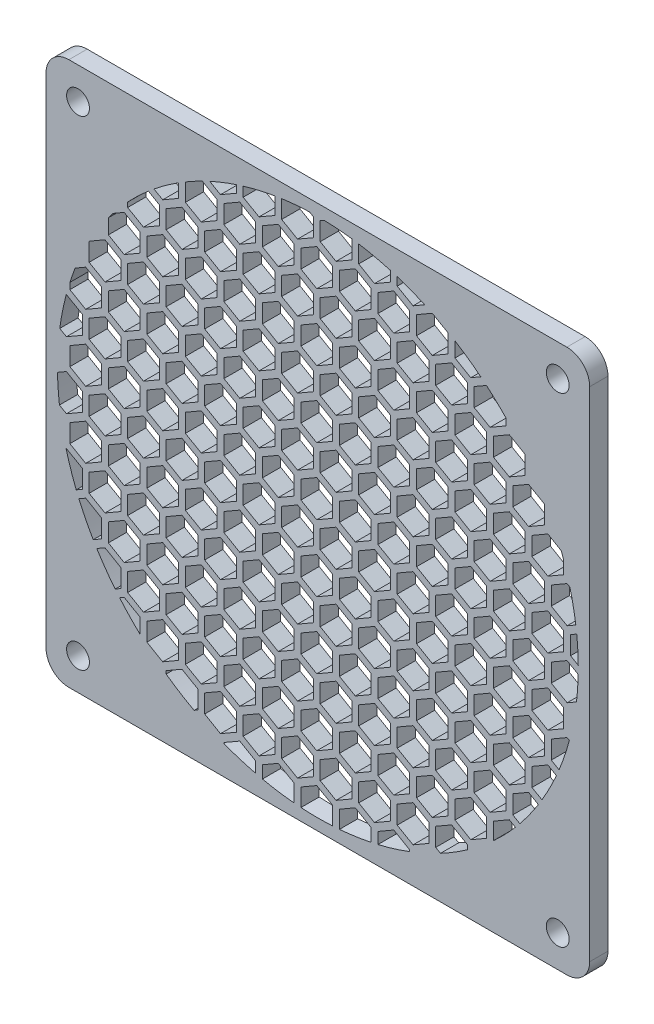
SolidWorks part; units mm, degrees
ref_plane "Plan de face" through (0, 0, 0) normal (0, 0, 1) x (1, 0, 0)
ref_plane "Plan de dessus" through (0, 0, 0) normal (0, 1, 0) x (1, 0, 0)
ref_plane "Plan de droite" through (0, 0, 0) normal (1, 0, 0) x (0, 0, -1)
sketch "Esquisse1" plane through (0, 0, 0) normal (0, 0, 1) x (1, 0, 0)
  line L1 (-59.5, 59.5) -> (59.5, 59.5)
  line L2 (-59.5, 59.5) -> (-59.5, -59.5)
  line L3 (-59.5, -59.5) -> (59.5, -59.5)
  line L4 (59.5, 59.5) -> (59.5, -59.5)
  line L5 (-59.5, 59.5) -> (59.5, -59.5) construction
  line L6 (-59.5, -59.5) -> (59.5, 59.5) construction
  line L47 (-30.4977, 48.1549) -> (-30.4977, 45.201)
  line L48 (-30.4977, 45.201) -> (-33.9618, 43.201)
  line L49 (-33.9618, 43.201) -> (-35.8669, 44.3009)
  line L58 (-25.3097, 51.0727) -> (-22.0677, 49.201)
  line L59 (-22.0677, 49.201) -> (-22.0677, 45.201)
  line L60 (-22.0677, 45.201) -> (-25.5318, 43.201)
  line L61 (-25.5318, 43.201) -> (-28.9959, 45.201)
  line L62 (-28.9959, 45.201) -> (-28.9959, 49.0738)
  line L66 (-17.8518, 54.1324) -> (-17.8518, 52.5)
  line L67 (-17.8518, 52.5) -> (-21.3159, 50.5)
  line L68 (-21.3159, 50.5) -> (-23.664, 51.8557)
  line L70 (-17.1018, 51.201) -> (-13.6377, 49.201)
  line L71 (-13.6377, 49.201) -> (-13.6377, 45.201)
  line L72 (-13.6377, 45.201) -> (-17.1018, 43.201)
  line L73 (-17.1018, 43.201) -> (-20.5659, 45.201)
  line L74 (-20.5659, 45.201) -> (-20.5659, 49.201)
  line L75 (-20.5659, 49.201) -> (-17.1018, 51.201)
  line L78 (-9.4218, 56.2159) -> (-9.4218, 52.5)
  line L79 (-9.4218, 52.5) -> (-12.8859, 50.5)
  line L80 (-12.8859, 50.5) -> (-16.35, 52.5)
  line L81 (-16.35, 52.5) -> (-16.35, 54.6047)
  line L82 (-8.6718, 51.201) -> (-5.2077, 49.201)
  line L83 (-5.2077, 49.201) -> (-5.2077, 45.201)
  line L84 (-5.2077, 45.201) -> (-8.6718, 43.201)
  line L85 (-8.6718, 43.201) -> (-12.1359, 45.201)
  line L86 (-12.1359, 45.201) -> (-12.1359, 49.201)
  line L87 (-12.1359, 49.201) -> (-8.6718, 51.201)
  line L89 (-1.8081, 56.9713) -> (-0.9918, 56.5)
  line L90 (-0.9918, 56.5) -> (-0.9918, 52.5)
  line L91 (-0.9918, 52.5) -> (-4.4559, 50.5)
  line L92 (-4.4559, 50.5) -> (-7.92, 52.5)
  line L93 (-7.92, 52.5) -> (-7.92, 56.4471)
  line L94 (-0.2418, 51.201) -> (3.2223, 49.201)
  line L95 (3.2223, 49.201) -> (3.2223, 45.201)
  line L96 (3.2223, 45.201) -> (-0.2418, 43.201)
  line L97 (-0.2418, 43.201) -> (-3.7059, 45.201)
  line L98 (-3.7059, 45.201) -> (-3.7059, 49.201)
  line L99 (-3.7059, 49.201) -> (-0.2418, 51.201)
  line L100 (0.51, 56.5) -> (1.3484, 56.984)
  line L101 (7.41, 56.5163) -> (7.4382, 56.5)
  line L102 (7.4382, 56.5) -> (7.4382, 52.5)
  line L103 (7.4382, 52.5) -> (3.9741, 50.5)
  line L104 (3.9741, 50.5) -> (0.51, 52.5)
  line L105 (0.51, 52.5) -> (0.51, 56.5)
  line L106 (8.1882, 51.201) -> (11.6523, 49.201)
  line L107 (11.6523, 49.201) -> (11.6523, 45.201)
  line L108 (11.6523, 45.201) -> (8.1882, 43.201)
  line L109 (8.1882, 43.201) -> (4.7241, 45.201)
  line L110 (4.7241, 45.201) -> (4.7241, 49.201)
  line L111 (4.7241, 49.201) -> (8.1882, 51.201)
  line L114 (15.8682, 54.7467) -> (15.8682, 52.5)
  line L115 (15.8682, 52.5) -> (12.4041, 50.5)
  line L116 (12.4041, 50.5) -> (8.94, 52.5)
  line L117 (8.94, 52.5) -> (8.94, 56.2946)
  line L118 (16.6182, 51.201) -> (20.0823, 49.201)
  line L119 (20.0823, 49.201) -> (20.0823, 45.201)
  line L120 (20.0823, 45.201) -> (16.6182, 43.201)
  line L121 (16.6182, 43.201) -> (13.1541, 45.201)
  line L122 (13.1541, 45.201) -> (13.1541, 49.201)
  line L123 (13.1541, 49.201) -> (16.6182, 51.201)
  line L127 (23.3941, 51.978) -> (20.8341, 50.5)
  line L128 (20.8341, 50.5) -> (17.37, 52.5)
  line L129 (17.37, 52.5) -> (17.37, 54.2889)
  line L130 (25.0482, 51.201) -> (28.5123, 49.201)
  line L131 (28.5123, 49.201) -> (28.5123, 45.201)
  line L132 (28.5123, 45.201) -> (25.0482, 43.201)
  line L133 (25.0482, 43.201) -> (21.5841, 45.201)
  line L134 (21.5841, 45.201) -> (21.5841, 49.201)
  line L135 (21.5841, 49.201) -> (25.0482, 51.201)
  line L144 (35.665, 44.4635) -> (33.4782, 43.201)
  line L145 (33.4782, 43.201) -> (30.0141, 45.201)
  line L146 (30.0141, 45.201) -> (30.0141, 48.4578)
  line L202 (-42.3918, 36.604) -> (-38.9277, 34.604)
  line L203 (-38.9277, 34.604) -> (-38.9277, 30.604)
  line L204 (-38.9277, 30.604) -> (-42.3918, 28.604)
  line L205 (-42.3918, 28.604) -> (-45.8559, 30.604)
  line L206 (-45.8559, 30.604) -> (-45.8559, 33.8561)
  line L207 (-44.8401, 35.1904) -> (-42.3918, 36.604)
  line L209 (-37.0941, 43.2785) -> (-34.7118, 41.903)
  line L210 (-34.7118, 41.903) -> (-34.7118, 37.903)
  line L211 (-34.7118, 37.903) -> (-38.1759, 35.903)
  line L212 (-38.1759, 35.903) -> (-41.64, 37.903)
  line L213 (-41.64, 37.903) -> (-41.64, 38.9244)
  line L214 (-33.9618, 36.604) -> (-30.4977, 34.604)
  line L215 (-30.4977, 34.604) -> (-30.4977, 30.604)
  line L216 (-30.4977, 30.604) -> (-33.9618, 28.604)
  line L217 (-33.9618, 28.604) -> (-37.4259, 30.604)
  line L218 (-37.4259, 30.604) -> (-37.4259, 34.604)
  line L219 (-37.4259, 34.604) -> (-33.9618, 36.604)
  line L220 (-33.21, 41.903) -> (-29.7459, 43.903)
  line L221 (-29.7459, 43.903) -> (-26.2818, 41.903)
  line L222 (-26.2818, 41.903) -> (-26.2818, 37.903)
  line L223 (-26.2818, 37.903) -> (-29.7459, 35.903)
  line L224 (-29.7459, 35.903) -> (-33.21, 37.903)
  line L225 (-33.21, 37.903) -> (-33.21, 41.903)
  line L226 (-25.5318, 36.604) -> (-22.0677, 34.604)
  line L227 (-22.0677, 34.604) -> (-22.0677, 30.604)
  line L228 (-22.0677, 30.604) -> (-25.5318, 28.604)
  line L229 (-25.5318, 28.604) -> (-28.9959, 30.604)
  line L230 (-28.9959, 30.604) -> (-28.9959, 34.604)
  line L231 (-28.9959, 34.604) -> (-25.5318, 36.604)
  line L232 (-24.78, 41.903) -> (-21.3159, 43.903)
  line L233 (-21.3159, 43.903) -> (-17.8518, 41.903)
  line L234 (-17.8518, 41.903) -> (-17.8518, 37.903)
  line L235 (-17.8518, 37.903) -> (-21.3159, 35.903)
  line L236 (-21.3159, 35.903) -> (-24.78, 37.903)
  line L237 (-24.78, 37.903) -> (-24.78, 41.903)
  line L238 (-17.1018, 36.604) -> (-13.6377, 34.604)
  line L239 (-13.6377, 34.604) -> (-13.6377, 30.604)
  line L240 (-13.6377, 30.604) -> (-17.1018, 28.604)
  line L241 (-17.1018, 28.604) -> (-20.5659, 30.604)
  line L242 (-20.5659, 30.604) -> (-20.5659, 34.604)
  line L243 (-20.5659, 34.604) -> (-17.1018, 36.604)
  line L244 (-16.35, 41.903) -> (-12.8859, 43.903)
  line L245 (-12.8859, 43.903) -> (-9.4218, 41.903)
  line L246 (-9.4218, 41.903) -> (-9.4218, 37.903)
  line L247 (-9.4218, 37.903) -> (-12.8859, 35.903)
  line L248 (-12.8859, 35.903) -> (-16.35, 37.903)
  line L249 (-16.35, 37.903) -> (-16.35, 41.903)
  line L250 (-8.6718, 36.604) -> (-5.2077, 34.604)
  line L251 (-5.2077, 34.604) -> (-5.2077, 30.604)
  line L252 (-5.2077, 30.604) -> (-8.6718, 28.604)
  line L253 (-8.6718, 28.604) -> (-12.1359, 30.604)
  line L254 (-12.1359, 30.604) -> (-12.1359, 34.604)
  line L255 (-12.1359, 34.604) -> (-8.6718, 36.604)
  line L256 (-7.92, 41.903) -> (-4.4559, 43.903)
  line L257 (-4.4559, 43.903) -> (-0.9918, 41.903)
  line L258 (-0.9918, 41.903) -> (-0.9918, 37.903)
  line L259 (-0.9918, 37.903) -> (-4.4559, 35.903)
  line L260 (-4.4559, 35.903) -> (-7.92, 37.903)
  line L261 (-7.92, 37.903) -> (-7.92, 41.903)
  line L262 (-0.2418, 36.604) -> (3.2223, 34.604)
  line L263 (3.2223, 34.604) -> (3.2223, 30.604)
  line L264 (3.2223, 30.604) -> (-0.2418, 28.604)
  line L265 (-0.2418, 28.604) -> (-3.7059, 30.604)
  line L266 (-3.7059, 30.604) -> (-3.7059, 34.604)
  line L267 (-3.7059, 34.604) -> (-0.2418, 36.604)
  line L268 (0.51, 41.903) -> (3.9741, 43.903)
  line L269 (3.9741, 43.903) -> (7.4382, 41.903)
  line L270 (7.4382, 41.903) -> (7.4382, 37.903)
  line L271 (7.4382, 37.903) -> (3.9741, 35.903)
  line L272 (3.9741, 35.903) -> (0.51, 37.903)
  line L273 (0.51, 37.903) -> (0.51, 41.903)
  line L274 (8.1882, 36.604) -> (11.6523, 34.604)
  line L275 (11.6523, 34.604) -> (11.6523, 30.604)
  line L276 (11.6523, 30.604) -> (8.1882, 28.604)
  line L277 (8.1882, 28.604) -> (4.7241, 30.604)
  line L278 (4.7241, 30.604) -> (4.7241, 34.604)
  line L279 (4.7241, 34.604) -> (8.1882, 36.604)
  line L280 (8.94, 41.903) -> (12.4041, 43.903)
  line L281 (12.4041, 43.903) -> (15.8682, 41.903)
  line L282 (15.8682, 41.903) -> (15.8682, 37.903)
  line L283 (15.8682, 37.903) -> (12.4041, 35.903)
  line L284 (12.4041, 35.903) -> (8.94, 37.903)
  line L285 (8.94, 37.903) -> (8.94, 41.903)
  line L286 (16.6182, 36.604) -> (20.0823, 34.604)
  line L287 (20.0823, 34.604) -> (20.0823, 30.604)
  line L288 (20.0823, 30.604) -> (16.6182, 28.604)
  line L289 (16.6182, 28.604) -> (13.1541, 30.604)
  line L290 (13.1541, 30.604) -> (13.1541, 34.604)
  line L291 (13.1541, 34.604) -> (16.6182, 36.604)
  line L292 (17.37, 41.903) -> (20.8341, 43.903)
  line L293 (20.8341, 43.903) -> (24.2982, 41.903)
  line L294 (24.2982, 41.903) -> (24.2982, 37.903)
  line L295 (24.2982, 37.903) -> (20.8341, 35.903)
  line L296 (20.8341, 35.903) -> (17.37, 37.903)
  line L297 (17.37, 37.903) -> (17.37, 41.903)
  line L298 (25.0482, 36.604) -> (28.5123, 34.604)
  line L299 (28.5123, 34.604) -> (28.5123, 30.604)
  line L300 (28.5123, 30.604) -> (25.0482, 28.604)
  line L301 (25.0482, 28.604) -> (21.5841, 30.604)
  line L302 (21.5841, 30.604) -> (21.5841, 34.604)
  line L303 (21.5841, 34.604) -> (25.0482, 36.604)
  line L304 (25.8, 41.903) -> (29.2641, 43.903)
  line L305 (29.2641, 43.903) -> (32.7282, 41.903)
  line L306 (32.7282, 41.903) -> (32.7282, 37.903)
  line L307 (32.7282, 37.903) -> (29.2641, 35.903)
  line L308 (29.2641, 35.903) -> (25.8, 37.903)
  line L309 (25.8, 37.903) -> (25.8, 41.903)
  line L310 (33.4782, 36.604) -> (36.9423, 34.604)
  line L311 (36.9423, 34.604) -> (36.9423, 30.604)
  line L312 (36.9423, 30.604) -> (33.4782, 28.604)
  line L313 (33.4782, 28.604) -> (30.0141, 30.604)
  line L314 (30.0141, 30.604) -> (30.0141, 34.604)
  line L315 (30.0141, 34.604) -> (33.4782, 36.604)
  line L316 (34.23, 41.903) -> (36.8997, 43.4444)
  line L319 (41.1582, 37.903) -> (37.6941, 35.903)
  line L320 (37.6941, 35.903) -> (34.23, 37.903)
  line L321 (34.23, 37.903) -> (34.23, 41.903)
  line L322 (41.9082, 36.604) -> (45.2324, 34.6847)
  line L323 (45.3723, 34.5015) -> (45.3723, 30.604)
  line L324 (45.3723, 30.604) -> (41.9082, 28.604)
  line L325 (41.9082, 28.604) -> (38.4441, 30.604)
  line L326 (38.4441, 30.604) -> (38.4441, 34.604)
  line L327 (38.4441, 34.604) -> (41.9082, 36.604)
  line L359 (-50.8218, 22.007) -> (-47.3577, 20.007)
  line L360 (-47.3577, 20.007) -> (-47.3577, 16.007)
  line L361 (-47.3577, 16.007) -> (-50.8218, 14.007)
  line L362 (-50.8218, 14.007) -> (-54.2859, 16.007)
  line L363 (-54.2859, 16.007) -> (-54.2859, 17.3793)
  line L364 (-53.1151, 20.6829) -> (-50.8218, 22.007)
  line L365 (-50.0171, 27.3365) -> (-46.6059, 29.306)
  line L366 (-46.6059, 29.306) -> (-43.1418, 27.306)
  line L367 (-43.1418, 27.306) -> (-43.1418, 23.306)
  line L368 (-43.1418, 23.306) -> (-46.6059, 21.306)
  line L369 (-46.6059, 21.306) -> (-50.07, 23.306)
  line L370 (-50.07, 23.306) -> (-50.07, 27.2396)
  line L371 (-42.3918, 22.007) -> (-38.9277, 20.007)
  line L372 (-38.9277, 20.007) -> (-38.9277, 16.007)
  line L373 (-38.9277, 16.007) -> (-42.3918, 14.007)
  line L374 (-42.3918, 14.007) -> (-45.8559, 16.007)
  line L375 (-45.8559, 16.007) -> (-45.8559, 20.007)
  line L376 (-45.8559, 20.007) -> (-42.3918, 22.007)
  line L377 (-41.64, 27.306) -> (-38.1759, 29.306)
  line L378 (-38.1759, 29.306) -> (-34.7118, 27.306)
  line L379 (-34.7118, 27.306) -> (-34.7118, 23.306)
  line L380 (-34.7118, 23.306) -> (-38.1759, 21.306)
  line L381 (-38.1759, 21.306) -> (-41.64, 23.306)
  line L382 (-41.64, 23.306) -> (-41.64, 27.306)
  line L383 (-33.9618, 22.007) -> (-30.4977, 20.007)
  line L384 (-30.4977, 20.007) -> (-30.4977, 16.007)
  line L385 (-30.4977, 16.007) -> (-33.9618, 14.007)
  line L386 (-33.9618, 14.007) -> (-37.4259, 16.007)
  line L387 (-37.4259, 16.007) -> (-37.4259, 20.007)
  line L388 (-37.4259, 20.007) -> (-33.9618, 22.007)
  line L389 (-33.21, 27.306) -> (-29.7459, 29.306)
  line L390 (-29.7459, 29.306) -> (-26.2818, 27.306)
  line L391 (-26.2818, 27.306) -> (-26.2818, 23.306)
  line L392 (-26.2818, 23.306) -> (-29.7459, 21.306)
  line L393 (-29.7459, 21.306) -> (-33.21, 23.306)
  line L394 (-33.21, 23.306) -> (-33.21, 27.306)
  line L395 (-25.5318, 22.007) -> (-22.0677, 20.007)
  line L396 (-22.0677, 20.007) -> (-22.0677, 16.007)
  line L397 (-22.0677, 16.007) -> (-25.5318, 14.007)
  line L398 (-25.5318, 14.007) -> (-28.9959, 16.007)
  line L399 (-28.9959, 16.007) -> (-28.9959, 20.007)
  line L400 (-28.9959, 20.007) -> (-25.5318, 22.007)
  line L401 (-24.78, 27.306) -> (-21.3159, 29.306)
  line L402 (-21.3159, 29.306) -> (-17.8518, 27.306)
  line L403 (-17.8518, 27.306) -> (-17.8518, 23.306)
  line L404 (-17.8518, 23.306) -> (-21.3159, 21.306)
  line L405 (-21.3159, 21.306) -> (-24.78, 23.306)
  line L406 (-24.78, 23.306) -> (-24.78, 27.306)
  line L407 (-17.1018, 22.007) -> (-13.6377, 20.007)
  line L408 (-13.6377, 20.007) -> (-13.6377, 16.007)
  line L409 (-13.6377, 16.007) -> (-17.1018, 14.007)
  line L410 (-17.1018, 14.007) -> (-20.5659, 16.007)
  line L411 (-20.5659, 16.007) -> (-20.5659, 20.007)
  line L412 (-20.5659, 20.007) -> (-17.1018, 22.007)
  line L413 (-16.35, 27.306) -> (-12.8859, 29.306)
  line L414 (-12.8859, 29.306) -> (-9.4218, 27.306)
  line L415 (-9.4218, 27.306) -> (-9.4218, 23.306)
  line L416 (-9.4218, 23.306) -> (-12.8859, 21.306)
  line L417 (-12.8859, 21.306) -> (-16.35, 23.306)
  line L418 (-16.35, 23.306) -> (-16.35, 27.306)
  line L419 (-8.6718, 22.007) -> (-5.2077, 20.007)
  line L420 (-5.2077, 20.007) -> (-5.2077, 16.007)
  line L421 (-5.2077, 16.007) -> (-8.6718, 14.007)
  line L422 (-8.6718, 14.007) -> (-12.1359, 16.007)
  line L423 (-12.1359, 16.007) -> (-12.1359, 20.007)
  line L424 (-12.1359, 20.007) -> (-8.6718, 22.007)
  line L425 (-7.92, 27.306) -> (-4.4559, 29.306)
  line L426 (-4.4559, 29.306) -> (-0.9918, 27.306)
  line L427 (-0.9918, 27.306) -> (-0.9918, 23.306)
  line L428 (-0.9918, 23.306) -> (-4.4559, 21.306)
  line L429 (-4.4559, 21.306) -> (-7.92, 23.306)
  line L430 (-7.92, 23.306) -> (-7.92, 27.306)
  line L431 (-0.2418, 22.007) -> (3.2223, 20.007)
  line L432 (3.2223, 20.007) -> (3.2223, 16.007)
  line L433 (3.2223, 16.007) -> (-0.2418, 14.007)
  line L434 (-0.2418, 14.007) -> (-3.7059, 16.007)
  line L435 (-3.7059, 16.007) -> (-3.7059, 20.007)
  line L436 (-3.7059, 20.007) -> (-0.2418, 22.007)
  line L437 (0.51, 27.306) -> (3.9741, 29.306)
  line L438 (3.9741, 29.306) -> (7.4382, 27.306)
  line L439 (7.4382, 27.306) -> (7.4382, 23.306)
  line L440 (7.4382, 23.306) -> (3.9741, 21.306)
  line L441 (3.9741, 21.306) -> (0.51, 23.306)
  line L442 (0.51, 23.306) -> (0.51, 27.306)
  line L443 (8.1882, 22.007) -> (11.6523, 20.007)
  line L444 (11.6523, 20.007) -> (11.6523, 16.007)
  line L445 (11.6523, 16.007) -> (8.1882, 14.007)
  line L446 (8.1882, 14.007) -> (4.7241, 16.007)
  line L447 (4.7241, 16.007) -> (4.7241, 20.007)
  line L448 (4.7241, 20.007) -> (8.1882, 22.007)
  line L449 (8.94, 27.306) -> (12.4041, 29.306)
  line L450 (12.4041, 29.306) -> (15.8682, 27.306)
  line L451 (15.8682, 27.306) -> (15.8682, 23.306)
  line L452 (15.8682, 23.306) -> (12.4041, 21.306)
  line L453 (12.4041, 21.306) -> (8.94, 23.306)
  line L454 (8.94, 23.306) -> (8.94, 27.306)
  line L455 (16.6182, 22.007) -> (20.0823, 20.007)
  line L456 (20.0823, 20.007) -> (20.0823, 16.007)
  line L457 (20.0823, 16.007) -> (16.6182, 14.007)
  line L458 (16.6182, 14.007) -> (13.1541, 16.007)
  line L459 (13.1541, 16.007) -> (13.1541, 20.007)
  line L460 (13.1541, 20.007) -> (16.6182, 22.007)
  line L461 (17.37, 27.306) -> (20.8341, 29.306)
  line L462 (20.8341, 29.306) -> (24.2982, 27.306)
  line L463 (24.2982, 27.306) -> (24.2982, 23.306)
  line L464 (24.2982, 23.306) -> (20.8341, 21.306)
  line L465 (20.8341, 21.306) -> (17.37, 23.306)
  line L466 (17.37, 23.306) -> (17.37, 27.306)
  line L467 (25.0482, 22.007) -> (28.5123, 20.007)
  line L468 (28.5123, 20.007) -> (28.5123, 16.007)
  line L469 (28.5123, 16.007) -> (25.0482, 14.007)
  line L470 (25.0482, 14.007) -> (21.5841, 16.007)
  line L471 (21.5841, 16.007) -> (21.5841, 20.007)
  line L472 (21.5841, 20.007) -> (25.0482, 22.007)
  line L473 (25.8, 27.306) -> (29.2641, 29.306)
  line L474 (29.2641, 29.306) -> (32.7282, 27.306)
  line L475 (32.7282, 27.306) -> (32.7282, 23.306)
  line L476 (32.7282, 23.306) -> (29.2641, 21.306)
  line L477 (29.2641, 21.306) -> (25.8, 23.306)
  line L478 (25.8, 23.306) -> (25.8, 27.306)
  line L479 (33.4782, 22.007) -> (36.9423, 20.007)
  line L480 (36.9423, 20.007) -> (36.9423, 16.007)
  line L481 (36.9423, 16.007) -> (33.4782, 14.007)
  line L482 (33.4782, 14.007) -> (30.0141, 16.007)
  line L483 (30.0141, 16.007) -> (30.0141, 20.007)
  line L484 (30.0141, 20.007) -> (33.4782, 22.007)
  line L485 (34.23, 27.306) -> (37.6941, 29.306)
  line L486 (37.6941, 29.306) -> (41.1582, 27.306)
  line L487 (41.1582, 27.306) -> (41.1582, 23.306)
  line L488 (41.1582, 23.306) -> (37.6941, 21.306)
  line L489 (37.6941, 21.306) -> (34.23, 23.306)
  line L490 (34.23, 23.306) -> (34.23, 27.306)
  line L491 (41.9082, 22.007) -> (45.3723, 20.007)
  line L492 (45.3723, 20.007) -> (45.3723, 16.007)
  line L493 (45.3723, 16.007) -> (41.9082, 14.007)
  line L494 (41.9082, 14.007) -> (38.4441, 16.007)
  line L495 (38.4441, 16.007) -> (38.4441, 20.007)
  line L496 (38.4441, 20.007) -> (41.9082, 22.007)
  line L497 (42.66, 27.306) -> (46.1241, 29.306)
  line L498 (46.1241, 29.306) -> (49.5882, 27.306)
  line L499 (49.5882, 27.306) -> (49.5882, 23.306)
  line L500 (49.5882, 23.306) -> (46.1241, 21.306)
  line L501 (46.1241, 21.306) -> (42.66, 23.306)
  line L502 (42.66, 23.306) -> (42.66, 27.306)
  line L503 (50.3382, 22.007) -> (53.2536, 20.3238)
  line L504 (53.8023, 18.8232) -> (53.8023, 16.007)
  line L505 (53.8023, 16.007) -> (50.3382, 14.007)
  line L506 (50.3382, 14.007) -> (46.8741, 16.007)
  line L507 (46.8741, 16.007) -> (46.8741, 20.007)
  line L508 (46.8741, 20.007) -> (50.3382, 22.007)
  line L522 (-55.0359, 14.709) -> (-51.5718, 12.709)
  line L523 (-51.5718, 12.709) -> (-51.5718, 8.709)
  line L524 (-51.5718, 8.709) -> (-55.0359, 6.709)
  line L525 (-55.0359, 6.709) -> (-56.4974, 7.5528)
  line L527 (-55.0756, 14.6861) -> (-55.0359, 14.709)
  line L528 (-50.8218, 7.41) -> (-47.3577, 5.41)
  line L529 (-47.3577, 5.41) -> (-47.3577, 1.41)
  line L530 (-47.3577, 1.41) -> (-50.8218, -0.59)
  line L531 (-50.8218, -0.59) -> (-54.2859, 1.41)
  line L532 (-54.2859, 1.41) -> (-54.2859, 5.41)
  line L533 (-54.2859, 5.41) -> (-50.8218, 7.41)
  line L534 (-50.07, 12.709) -> (-46.6059, 14.709)
  line L535 (-46.6059, 14.709) -> (-43.1418, 12.709)
  line L536 (-43.1418, 12.709) -> (-43.1418, 8.709)
  line L537 (-43.1418, 8.709) -> (-46.6059, 6.709)
  line L538 (-46.6059, 6.709) -> (-50.07, 8.709)
  line L539 (-50.07, 8.709) -> (-50.07, 12.709)
  line L540 (-42.3918, 7.41) -> (-38.9277, 5.41)
  line L541 (-38.9277, 5.41) -> (-38.9277, 1.41)
  line L542 (-38.9277, 1.41) -> (-42.3918, -0.59)
  line L543 (-42.3918, -0.59) -> (-45.8559, 1.41)
  line L544 (-45.8559, 1.41) -> (-45.8559, 5.41)
  line L545 (-45.8559, 5.41) -> (-42.3918, 7.41)
  line L546 (-41.64, 12.709) -> (-38.1759, 14.709)
  line L547 (-38.1759, 14.709) -> (-34.7118, 12.709)
  line L548 (-34.7118, 12.709) -> (-34.7118, 8.709)
  line L549 (-34.7118, 8.709) -> (-38.1759, 6.709)
  line L550 (-38.1759, 6.709) -> (-41.64, 8.709)
  line L551 (-41.64, 8.709) -> (-41.64, 12.709)
  line L552 (-33.9618, 7.41) -> (-30.4977, 5.41)
  line L553 (-30.4977, 5.41) -> (-30.4977, 1.41)
  line L554 (-30.4977, 1.41) -> (-33.9618, -0.59)
  line L555 (-33.9618, -0.59) -> (-37.4259, 1.41)
  line L556 (-37.4259, 1.41) -> (-37.4259, 5.41)
  line L557 (-37.4259, 5.41) -> (-33.9618, 7.41)
  line L558 (-33.21, 12.709) -> (-29.7459, 14.709)
  line L559 (-29.7459, 14.709) -> (-26.2818, 12.709)
  line L560 (-26.2818, 12.709) -> (-26.2818, 8.709)
  line L561 (-26.2818, 8.709) -> (-29.7459, 6.709)
  line L562 (-29.7459, 6.709) -> (-33.21, 8.709)
  line L563 (-33.21, 8.709) -> (-33.21, 12.709)
  line L564 (-25.5318, 7.41) -> (-22.0677, 5.41)
  line L565 (-22.0677, 5.41) -> (-22.0677, 1.41)
  line L566 (-22.0677, 1.41) -> (-25.5318, -0.59)
  line L567 (-25.5318, -0.59) -> (-28.9959, 1.41)
  line L568 (-28.9959, 1.41) -> (-28.9959, 5.41)
  line L569 (-28.9959, 5.41) -> (-25.5318, 7.41)
  line L570 (-24.78, 12.709) -> (-21.3159, 14.709)
  line L571 (-21.3159, 14.709) -> (-17.8518, 12.709)
  line L572 (-17.8518, 12.709) -> (-17.8518, 8.709)
  line L573 (-17.8518, 8.709) -> (-21.3159, 6.709)
  line L574 (-21.3159, 6.709) -> (-24.78, 8.709)
  line L575 (-24.78, 8.709) -> (-24.78, 12.709)
  line L576 (-17.1018, 7.41) -> (-13.6377, 5.41)
  line L577 (-13.6377, 5.41) -> (-13.6377, 1.41)
  line L578 (-13.6377, 1.41) -> (-17.1018, -0.59)
  line L579 (-17.1018, -0.59) -> (-20.5659, 1.41)
  line L580 (-20.5659, 1.41) -> (-20.5659, 5.41)
  line L581 (-20.5659, 5.41) -> (-17.1018, 7.41)
  line L582 (-16.35, 12.709) -> (-12.8859, 14.709)
  line L583 (-12.8859, 14.709) -> (-9.4218, 12.709)
  line L584 (-9.4218, 12.709) -> (-9.4218, 8.709)
  line L585 (-9.4218, 8.709) -> (-12.8859, 6.709)
  line L586 (-12.8859, 6.709) -> (-16.35, 8.709)
  line L587 (-16.35, 8.709) -> (-16.35, 12.709)
  line L588 (-8.6718, 7.41) -> (-5.2077, 5.41)
  line L589 (-5.2077, 5.41) -> (-5.2077, 1.41)
  line L590 (-5.2077, 1.41) -> (-8.6718, -0.59)
  line L591 (-8.6718, -0.59) -> (-12.1359, 1.41)
  line L592 (-12.1359, 1.41) -> (-12.1359, 5.41)
  line L593 (-12.1359, 5.41) -> (-8.6718, 7.41)
  line L594 (-7.92, 12.709) -> (-4.4559, 14.709)
  line L595 (-4.4559, 14.709) -> (-0.9918, 12.709)
  line L596 (-0.9918, 12.709) -> (-0.9918, 8.709)
  line L597 (-0.9918, 8.709) -> (-4.4559, 6.709)
  line L598 (-4.4559, 6.709) -> (-7.92, 8.709)
  line L599 (-7.92, 8.709) -> (-7.92, 12.709)
  line L600 (-0.2418, 7.41) -> (3.2223, 5.41)
  line L601 (3.2223, 5.41) -> (3.2223, 1.41)
  line L602 (3.2223, 1.41) -> (-0.2418, -0.59)
  line L603 (-0.2418, -0.59) -> (-3.7059, 1.41)
  line L604 (-3.7059, 1.41) -> (-3.7059, 5.41)
  line L605 (-3.7059, 5.41) -> (-0.2418, 7.41)
  line L606 (0.51, 12.709) -> (3.9741, 14.709)
  line L607 (3.9741, 14.709) -> (7.4382, 12.709)
  line L608 (7.4382, 12.709) -> (7.4382, 8.709)
  line L609 (7.4382, 8.709) -> (3.9741, 6.709)
  line L610 (3.9741, 6.709) -> (0.51, 8.709)
  line L611 (0.51, 8.709) -> (0.51, 12.709)
  line L612 (8.1882, 7.41) -> (11.6523, 5.41)
  line L613 (11.6523, 5.41) -> (11.6523, 1.41)
  line L614 (11.6523, 1.41) -> (8.1882, -0.59)
  line L615 (8.1882, -0.59) -> (4.7241, 1.41)
  line L616 (4.7241, 1.41) -> (4.7241, 5.41)
  line L617 (4.7241, 5.41) -> (8.1882, 7.41)
  line L618 (8.94, 12.709) -> (12.4041, 14.709)
  line L619 (12.4041, 14.709) -> (15.8682, 12.709)
  line L620 (15.8682, 12.709) -> (15.8682, 8.709)
  line L621 (15.8682, 8.709) -> (12.4041, 6.709)
  line L622 (12.4041, 6.709) -> (8.94, 8.709)
  line L623 (8.94, 8.709) -> (8.94, 12.709)
  line L624 (16.6182, 7.41) -> (20.0823, 5.41)
  line L625 (20.0823, 5.41) -> (20.0823, 1.41)
  line L626 (20.0823, 1.41) -> (16.6182, -0.59)
  line L627 (16.6182, -0.59) -> (13.1541, 1.41)
  line L628 (13.1541, 1.41) -> (13.1541, 5.41)
  line L629 (13.1541, 5.41) -> (16.6182, 7.41)
  line L630 (17.37, 12.709) -> (20.8341, 14.709)
  line L631 (20.8341, 14.709) -> (24.2982, 12.709)
  line L632 (24.2982, 12.709) -> (24.2982, 8.709)
  line L633 (24.2982, 8.709) -> (20.8341, 6.709)
  line L634 (20.8341, 6.709) -> (17.37, 8.709)
  line L635 (17.37, 8.709) -> (17.37, 12.709)
  line L636 (25.0482, 7.41) -> (28.5123, 5.41)
  line L637 (28.5123, 5.41) -> (28.5123, 1.41)
  line L638 (28.5123, 1.41) -> (25.0482, -0.59)
  line L639 (25.0482, -0.59) -> (21.5841, 1.41)
  line L640 (21.5841, 1.41) -> (21.5841, 5.41)
  line L641 (21.5841, 5.41) -> (25.0482, 7.41)
  line L642 (25.8, 12.709) -> (29.2641, 14.709)
  line L643 (29.2641, 14.709) -> (32.7282, 12.709)
  line L644 (32.7282, 12.709) -> (32.7282, 8.709)
  line L645 (32.7282, 8.709) -> (29.2641, 6.709)
  line L646 (29.2641, 6.709) -> (25.8, 8.709)
  line L647 (25.8, 8.709) -> (25.8, 12.709)
  line L648 (33.4782, 7.41) -> (36.9423, 5.41)
  line L649 (36.9423, 5.41) -> (36.9423, 1.41)
  line L650 (36.9423, 1.41) -> (33.4782, -0.59)
  line L651 (33.4782, -0.59) -> (30.0141, 1.41)
  line L652 (30.0141, 1.41) -> (30.0141, 5.41)
  line L653 (30.0141, 5.41) -> (33.4782, 7.41)
  line L654 (34.23, 12.709) -> (37.6941, 14.709)
  line L655 (37.6941, 14.709) -> (41.1582, 12.709)
  line L656 (41.1582, 12.709) -> (41.1582, 8.709)
  line L657 (41.1582, 8.709) -> (37.6941, 6.709)
  line L658 (37.6941, 6.709) -> (34.23, 8.709)
  line L659 (34.23, 8.709) -> (34.23, 12.709)
  line L660 (41.9082, 7.41) -> (45.3723, 5.41)
  line L661 (45.3723, 5.41) -> (45.3723, 1.41)
  line L662 (45.3723, 1.41) -> (41.9082, -0.59)
  line L663 (41.9082, -0.59) -> (38.4441, 1.41)
  line L664 (38.4441, 1.41) -> (38.4441, 5.41)
  line L665 (38.4441, 5.41) -> (41.9082, 7.41)
  line L666 (42.66, 12.709) -> (46.1241, 14.709)
  line L667 (46.1241, 14.709) -> (49.5882, 12.709)
  line L668 (49.5882, 12.709) -> (49.5882, 8.709)
  line L669 (49.5882, 8.709) -> (46.1241, 6.709)
  line L670 (46.1241, 6.709) -> (42.66, 8.709)
  line L671 (42.66, 8.709) -> (42.66, 12.709)
  line L672 (50.3382, 7.41) -> (53.8023, 5.41)
  line L673 (53.8023, 5.41) -> (53.8023, 1.41)
  line L674 (53.8023, 1.41) -> (50.3382, -0.59)
  line L675 (50.3382, -0.59) -> (46.8741, 1.41)
  line L676 (46.8741, 1.41) -> (46.8741, 5.41)
  line L677 (46.8741, 5.41) -> (50.3382, 7.41)
  line L678 (51.09, 12.709) -> (54.5541, 14.709)
  line L679 (54.5541, 14.709) -> (55.162, 14.358)
  line L681 (56.4623, 7.8107) -> (54.5541, 6.709)
  line L682 (54.5541, 6.709) -> (51.09, 8.709)
  line L683 (51.09, 8.709) -> (51.09, 12.709)
  line L687 (56.9984, 0.4318) -> (55.3041, 1.41)
  line L688 (55.3041, 1.41) -> (55.3041, 5.41)
  line L689 (55.3041, 5.41) -> (56.6624, 6.1942)
  line L691 (-55.0359, 0.112) -> (-51.5718, -1.888)
  line L692 (-51.5718, -1.888) -> (-51.5718, -5.888)
  line L693 (-51.5718, -5.888) -> (-55.0359, -7.888)
  line L694 (-55.0359, -7.888) -> (-56.5681, -7.0034)
  line L696 (-56.9909, -1.0167) -> (-55.0359, 0.112)
  line L697 (-50.8218, -7.187) -> (-47.3577, -9.187)
  line L698 (-47.3577, -9.187) -> (-47.3577, -13.187)
  line L699 (-47.3577, -13.187) -> (-50.8218, -15.187)
  line L700 (-50.8218, -15.187) -> (-54.2859, -13.187)
  line L701 (-54.2859, -13.187) -> (-54.2859, -9.187)
  line L702 (-54.2859, -9.187) -> (-50.8218, -7.187)
  line L703 (-50.07, -1.888) -> (-46.6059, 0.112)
  line L704 (-46.6059, 0.112) -> (-43.1418, -1.888)
  line L705 (-43.1418, -1.888) -> (-43.1418, -5.888)
  line L706 (-43.1418, -5.888) -> (-46.6059, -7.888)
  line L707 (-46.6059, -7.888) -> (-50.07, -5.888)
  line L708 (-50.07, -5.888) -> (-50.07, -1.888)
  line L709 (-42.3918, -7.187) -> (-38.9277, -9.187)
  line L710 (-38.9277, -9.187) -> (-38.9277, -13.187)
  line L711 (-38.9277, -13.187) -> (-42.3918, -15.187)
  line L712 (-42.3918, -15.187) -> (-45.8559, -13.187)
  line L713 (-45.8559, -13.187) -> (-45.8559, -9.187)
  line L714 (-45.8559, -9.187) -> (-42.3918, -7.187)
  line L715 (-41.64, -1.888) -> (-38.1759, 0.112)
  line L716 (-38.1759, 0.112) -> (-34.7118, -1.888)
  line L717 (-34.7118, -1.888) -> (-34.7118, -5.888)
  line L718 (-34.7118, -5.888) -> (-38.1759, -7.888)
  line L719 (-38.1759, -7.888) -> (-41.64, -5.888)
  line L720 (-41.64, -5.888) -> (-41.64, -1.888)
  line L721 (-33.9618, -7.187) -> (-30.4977, -9.187)
  line L722 (-30.4977, -9.187) -> (-30.4977, -13.187)
  line L723 (-30.4977, -13.187) -> (-33.9618, -15.187)
  line L724 (-33.9618, -15.187) -> (-37.4259, -13.187)
  line L725 (-37.4259, -13.187) -> (-37.4259, -9.187)
  line L726 (-37.4259, -9.187) -> (-33.9618, -7.187)
  line L727 (-33.21, -1.888) -> (-29.7459, 0.112)
  line L728 (-29.7459, 0.112) -> (-26.2818, -1.888)
  line L729 (-26.2818, -1.888) -> (-26.2818, -5.888)
  line L730 (-26.2818, -5.888) -> (-29.7459, -7.888)
  line L731 (-29.7459, -7.888) -> (-33.21, -5.888)
  line L732 (-33.21, -5.888) -> (-33.21, -1.888)
  line L733 (-25.5318, -7.187) -> (-22.0677, -9.187)
  line L734 (-22.0677, -9.187) -> (-22.0677, -13.187)
  line L735 (-22.0677, -13.187) -> (-25.5318, -15.187)
  line L736 (-25.5318, -15.187) -> (-28.9959, -13.187)
  line L737 (-28.9959, -13.187) -> (-28.9959, -9.187)
  line L738 (-28.9959, -9.187) -> (-25.5318, -7.187)
  line L739 (-24.78, -1.888) -> (-21.3159, 0.112)
  line L740 (-21.3159, 0.112) -> (-17.8518, -1.888)
  line L741 (-17.8518, -1.888) -> (-17.8518, -5.888)
  line L742 (-17.8518, -5.888) -> (-21.3159, -7.888)
  line L743 (-21.3159, -7.888) -> (-24.78, -5.888)
  line L744 (-24.78, -5.888) -> (-24.78, -1.888)
  line L745 (-17.1018, -7.187) -> (-13.6377, -9.187)
  line L746 (-13.6377, -9.187) -> (-13.6377, -13.187)
  line L747 (-13.6377, -13.187) -> (-17.1018, -15.187)
  line L748 (-17.1018, -15.187) -> (-20.5659, -13.187)
  line L749 (-20.5659, -13.187) -> (-20.5659, -9.187)
  line L750 (-20.5659, -9.187) -> (-17.1018, -7.187)
  line L751 (-16.35, -1.888) -> (-12.8859, 0.112)
  line L752 (-12.8859, 0.112) -> (-9.4218, -1.888)
  line L753 (-9.4218, -1.888) -> (-9.4218, -5.888)
  line L754 (-9.4218, -5.888) -> (-12.8859, -7.888)
  line L755 (-12.8859, -7.888) -> (-16.35, -5.888)
  line L756 (-16.35, -5.888) -> (-16.35, -1.888)
  line L757 (-8.6718, -7.187) -> (-5.2077, -9.187)
  line L758 (-5.2077, -9.187) -> (-5.2077, -13.187)
  line L759 (-5.2077, -13.187) -> (-8.6718, -15.187)
  line L760 (-8.6718, -15.187) -> (-12.1359, -13.187)
  line L761 (-12.1359, -13.187) -> (-12.1359, -9.187)
  line L762 (-12.1359, -9.187) -> (-8.6718, -7.187)
  line L763 (-7.92, -1.888) -> (-4.4559, 0.112)
  line L764 (-4.4559, 0.112) -> (-0.9918, -1.888)
  line L765 (-0.9918, -1.888) -> (-0.9918, -5.888)
  line L766 (-0.9918, -5.888) -> (-4.4559, -7.888)
  line L767 (-4.4559, -7.888) -> (-7.92, -5.888)
  line L768 (-7.92, -5.888) -> (-7.92, -1.888)
  line L769 (-0.2418, -7.187) -> (3.2223, -9.187)
  line L770 (3.2223, -9.187) -> (3.2223, -13.187)
  line L771 (3.2223, -13.187) -> (-0.2418, -15.187)
  line L772 (-0.2418, -15.187) -> (-3.7059, -13.187)
  line L773 (-3.7059, -13.187) -> (-3.7059, -9.187)
  line L774 (-3.7059, -9.187) -> (-0.2418, -7.187)
  line L775 (0.51, -1.888) -> (3.9741, 0.112)
  line L776 (3.9741, 0.112) -> (7.4382, -1.888)
  line L777 (7.4382, -1.888) -> (7.4382, -5.888)
  line L778 (7.4382, -5.888) -> (3.9741, -7.888)
  line L779 (3.9741, -7.888) -> (0.51, -5.888)
  line L780 (0.51, -5.888) -> (0.51, -1.888)
  line L781 (8.1882, -7.187) -> (11.6523, -9.187)
  line L782 (11.6523, -9.187) -> (11.6523, -13.187)
  line L783 (11.6523, -13.187) -> (8.1882, -15.187)
  line L784 (8.1882, -15.187) -> (4.7241, -13.187)
  line L785 (4.7241, -13.187) -> (4.7241, -9.187)
  line L786 (4.7241, -9.187) -> (8.1882, -7.187)
  line L787 (8.94, -1.888) -> (12.4041, 0.112)
  line L788 (12.4041, 0.112) -> (15.8682, -1.888)
  line L789 (15.8682, -1.888) -> (15.8682, -5.888)
  line L790 (15.8682, -5.888) -> (12.4041, -7.888)
  line L791 (12.4041, -7.888) -> (8.94, -5.888)
  line L792 (8.94, -5.888) -> (8.94, -1.888)
  line L793 (16.6182, -7.187) -> (20.0823, -9.187)
  line L794 (20.0823, -9.187) -> (20.0823, -13.187)
  line L795 (20.0823, -13.187) -> (16.6182, -15.187)
  line L796 (16.6182, -15.187) -> (13.1541, -13.187)
  line L797 (13.1541, -13.187) -> (13.1541, -9.187)
  line L798 (13.1541, -9.187) -> (16.6182, -7.187)
  line L799 (17.37, -1.888) -> (20.8341, 0.112)
  line L800 (20.8341, 0.112) -> (24.2982, -1.888)
  line L801 (24.2982, -1.888) -> (24.2982, -5.888)
  line L802 (24.2982, -5.888) -> (20.8341, -7.888)
  line L803 (20.8341, -7.888) -> (17.37, -5.888)
  line L804 (17.37, -5.888) -> (17.37, -1.888)
  line L805 (25.0482, -7.187) -> (28.5123, -9.187)
  line L806 (28.5123, -9.187) -> (28.5123, -13.187)
  line L807 (28.5123, -13.187) -> (25.0482, -15.187)
  line L808 (25.0482, -15.187) -> (21.5841, -13.187)
  line L809 (21.5841, -13.187) -> (21.5841, -9.187)
  line L810 (21.5841, -9.187) -> (25.0482, -7.187)
  line L811 (25.8, -1.888) -> (29.2641, 0.112)
  line L812 (29.2641, 0.112) -> (32.7282, -1.888)
  line L813 (32.7282, -1.888) -> (32.7282, -5.888)
  line L814 (32.7282, -5.888) -> (29.2641, -7.888)
  line L815 (29.2641, -7.888) -> (25.8, -5.888)
  line L816 (25.8, -5.888) -> (25.8, -1.888)
  line L817 (33.4782, -7.187) -> (36.9423, -9.187)
  line L818 (36.9423, -9.187) -> (36.9423, -13.187)
  line L819 (36.9423, -13.187) -> (33.4782, -15.187)
  line L820 (33.4782, -15.187) -> (30.0141, -13.187)
  line L821 (30.0141, -13.187) -> (30.0141, -9.187)
  line L822 (30.0141, -9.187) -> (33.4782, -7.187)
  line L823 (34.23, -1.888) -> (37.6941, 0.112)
  line L824 (37.6941, 0.112) -> (41.1582, -1.888)
  line L825 (41.1582, -1.888) -> (41.1582, -5.888)
  line L826 (41.1582, -5.888) -> (37.6941, -7.888)
  line L827 (37.6941, -7.888) -> (34.23, -5.888)
  line L828 (34.23, -5.888) -> (34.23, -1.888)
  line L829 (41.9082, -7.187) -> (45.3723, -9.187)
  line L830 (45.3723, -9.187) -> (45.3723, -13.187)
  line L831 (45.3723, -13.187) -> (41.9082, -15.187)
  line L832 (41.9082, -15.187) -> (38.4441, -13.187)
  line L833 (38.4441, -13.187) -> (38.4441, -9.187)
  line L834 (38.4441, -9.187) -> (41.9082, -7.187)
  line L835 (42.66, -1.888) -> (46.1241, 0.112)
  line L836 (46.1241, 0.112) -> (49.5882, -1.888)
  line L837 (49.5882, -1.888) -> (49.5882, -5.888)
  line L838 (49.5882, -5.888) -> (46.1241, -7.888)
  line L839 (46.1241, -7.888) -> (42.66, -5.888)
  line L840 (42.66, -5.888) -> (42.66, -1.888)
  line L841 (50.3382, -7.187) -> (53.8023, -9.187)
  line L842 (53.8023, -9.187) -> (53.8023, -13.187)
  line L843 (53.8023, -13.187) -> (50.3382, -15.187)
  line L844 (50.3382, -15.187) -> (46.8741, -13.187)
  line L845 (46.8741, -13.187) -> (46.8741, -9.187)
  line L846 (46.8741, -9.187) -> (50.3382, -7.187)
  line L847 (51.09, -1.888) -> (54.5541, 0.112)
  line L848 (54.5541, 0.112) -> (56.9854, -1.2917)
  line L850 (56.6044, -6.7043) -> (54.5541, -7.888)
  line L851 (54.5541, -7.888) -> (51.09, -5.888)
  line L852 (51.09, -5.888) -> (51.09, -1.888)
  line L860 (-55.0359, -14.485) -> (-51.5718, -16.485)
  line L861 (-51.5718, -16.485) -> (-51.5718, -20.485)
  line L862 (-51.5718, -20.485) -> (-52.8919, -21.2472)
  line L865 (-55.1165, -14.5316) -> (-55.0359, -14.485)
  line L866 (-50.8218, -21.784) -> (-47.3577, -23.784)
  line L867 (-47.3577, -23.784) -> (-47.3577, -27.784)
  line L868 (-47.3577, -27.784) -> (-49.1709, -28.8309)
  line L871 (-52.3096, -22.643) -> (-50.8218, -21.784)
  line L872 (-50.07, -16.485) -> (-46.6059, -14.485)
  line L873 (-46.6059, -14.485) -> (-43.1418, -16.485)
  line L874 (-43.1418, -16.485) -> (-43.1418, -20.485)
  line L875 (-43.1418, -20.485) -> (-46.6059, -22.485)
  line L876 (-46.6059, -22.485) -> (-50.07, -20.485)
  line L877 (-50.07, -20.485) -> (-50.07, -16.485)
  line L878 (-42.3918, -21.784) -> (-38.9277, -23.784)
  line L879 (-38.9277, -23.784) -> (-38.9277, -27.784)
  line L880 (-38.9277, -27.784) -> (-42.3918, -29.784)
  line L881 (-42.3918, -29.784) -> (-45.8559, -27.784)
  line L882 (-45.8559, -27.784) -> (-45.8559, -23.784)
  line L883 (-45.8559, -23.784) -> (-42.3918, -21.784)
  line L884 (-41.64, -16.485) -> (-38.1759, -14.485)
  line L885 (-38.1759, -14.485) -> (-34.7118, -16.485)
  line L886 (-34.7118, -16.485) -> (-34.7118, -20.485)
  line L887 (-34.7118, -20.485) -> (-38.1759, -22.485)
  line L888 (-38.1759, -22.485) -> (-41.64, -20.485)
  line L889 (-41.64, -20.485) -> (-41.64, -16.485)
  line L890 (-33.9618, -21.784) -> (-30.4977, -23.784)
  line L891 (-30.4977, -23.784) -> (-30.4977, -27.784)
  line L892 (-30.4977, -27.784) -> (-33.9618, -29.784)
  line L893 (-33.9618, -29.784) -> (-37.4259, -27.784)
  line L894 (-37.4259, -27.784) -> (-37.4259, -23.784)
  line L895 (-37.4259, -23.784) -> (-33.9618, -21.784)
  line L896 (-33.21, -16.485) -> (-29.7459, -14.485)
  line L897 (-29.7459, -14.485) -> (-26.2818, -16.485)
  line L898 (-26.2818, -16.485) -> (-26.2818, -20.485)
  line L899 (-26.2818, -20.485) -> (-29.7459, -22.485)
  line L900 (-29.7459, -22.485) -> (-33.21, -20.485)
  line L901 (-33.21, -20.485) -> (-33.21, -16.485)
  line L902 (-25.5318, -21.784) -> (-22.0677, -23.784)
  line L903 (-22.0677, -23.784) -> (-22.0677, -27.784)
  line L904 (-22.0677, -27.784) -> (-25.5318, -29.784)
  line L905 (-25.5318, -29.784) -> (-28.9959, -27.784)
  line L906 (-28.9959, -27.784) -> (-28.9959, -23.784)
  line L907 (-28.9959, -23.784) -> (-25.5318, -21.784)
  line L908 (-24.78, -16.485) -> (-21.3159, -14.485)
  line L909 (-21.3159, -14.485) -> (-17.8518, -16.485)
  line L910 (-17.8518, -16.485) -> (-17.8518, -20.485)
  line L911 (-17.8518, -20.485) -> (-21.3159, -22.485)
  line L912 (-21.3159, -22.485) -> (-24.78, -20.485)
  line L913 (-24.78, -20.485) -> (-24.78, -16.485)
  line L914 (-17.1018, -21.784) -> (-13.6377, -23.784)
  line L915 (-13.6377, -23.784) -> (-13.6377, -27.784)
  line L916 (-13.6377, -27.784) -> (-17.1018, -29.784)
  line L917 (-17.1018, -29.784) -> (-20.5659, -27.784)
  line L918 (-20.5659, -27.784) -> (-20.5659, -23.784)
  line L919 (-20.5659, -23.784) -> (-17.1018, -21.784)
  line L920 (-16.35, -16.485) -> (-12.8859, -14.485)
  line L921 (-12.8859, -14.485) -> (-9.4218, -16.485)
  line L922 (-9.4218, -16.485) -> (-9.4218, -20.485)
  line L923 (-9.4218, -20.485) -> (-12.8859, -22.485)
  line L924 (-12.8859, -22.485) -> (-16.35, -20.485)
  line L925 (-16.35, -20.485) -> (-16.35, -16.485)
  line L926 (-8.6718, -21.784) -> (-5.2077, -23.784)
  line L927 (-5.2077, -23.784) -> (-5.2077, -27.784)
  line L928 (-5.2077, -27.784) -> (-8.6718, -29.784)
  line L929 (-8.6718, -29.784) -> (-12.1359, -27.784)
  line L930 (-12.1359, -27.784) -> (-12.1359, -23.784)
  line L931 (-12.1359, -23.784) -> (-8.6718, -21.784)
  line L932 (-7.92, -16.485) -> (-4.4559, -14.485)
  line L933 (-4.4559, -14.485) -> (-0.9918, -16.485)
  line L934 (-0.9918, -16.485) -> (-0.9918, -20.485)
  line L935 (-0.9918, -20.485) -> (-4.4559, -22.485)
  line L936 (-4.4559, -22.485) -> (-7.92, -20.485)
  line L937 (-7.92, -20.485) -> (-7.92, -16.485)
  line L938 (-0.2418, -21.784) -> (3.2223, -23.784)
  line L939 (3.2223, -23.784) -> (3.2223, -27.784)
  line L940 (3.2223, -27.784) -> (-0.2418, -29.784)
  line L941 (-0.2418, -29.784) -> (-3.7059, -27.784)
  line L942 (-3.7059, -27.784) -> (-3.7059, -23.784)
  line L943 (-3.7059, -23.784) -> (-0.2418, -21.784)
  line L944 (0.51, -16.485) -> (3.9741, -14.485)
  line L945 (3.9741, -14.485) -> (7.4382, -16.485)
  line L946 (7.4382, -16.485) -> (7.4382, -20.485)
  line L947 (7.4382, -20.485) -> (3.9741, -22.485)
  line L948 (3.9741, -22.485) -> (0.51, -20.485)
  line L949 (0.51, -20.485) -> (0.51, -16.485)
  line L950 (8.1882, -21.784) -> (11.6523, -23.784)
  line L951 (11.6523, -23.784) -> (11.6523, -27.784)
  line L952 (11.6523, -27.784) -> (8.1882, -29.784)
  line L953 (8.1882, -29.784) -> (4.7241, -27.784)
  line L954 (4.7241, -27.784) -> (4.7241, -23.784)
  line L955 (4.7241, -23.784) -> (8.1882, -21.784)
  line L956 (8.94, -16.485) -> (12.4041, -14.485)
  line L957 (12.4041, -14.485) -> (15.8682, -16.485)
  line L958 (15.8682, -16.485) -> (15.8682, -20.485)
  line L959 (15.8682, -20.485) -> (12.4041, -22.485)
  line L960 (12.4041, -22.485) -> (8.94, -20.485)
  line L961 (8.94, -20.485) -> (8.94, -16.485)
  line L962 (16.6182, -21.784) -> (20.0823, -23.784)
  line L963 (20.0823, -23.784) -> (20.0823, -27.784)
  line L964 (20.0823, -27.784) -> (16.6182, -29.784)
  line L965 (16.6182, -29.784) -> (13.1541, -27.784)
  line L966 (13.1541, -27.784) -> (13.1541, -23.784)
  line L967 (13.1541, -23.784) -> (16.6182, -21.784)
  line L968 (17.37, -16.485) -> (20.8341, -14.485)
  line L969 (20.8341, -14.485) -> (24.2982, -16.485)
  line L970 (24.2982, -16.485) -> (24.2982, -20.485)
  line L971 (24.2982, -20.485) -> (20.8341, -22.485)
  line L972 (20.8341, -22.485) -> (17.37, -20.485)
  line L973 (17.37, -20.485) -> (17.37, -16.485)
  line L974 (25.0482, -21.784) -> (28.5123, -23.784)
  line L975 (28.5123, -23.784) -> (28.5123, -27.784)
  line L976 (28.5123, -27.784) -> (25.0482, -29.784)
  line L977 (25.0482, -29.784) -> (21.5841, -27.784)
  line L978 (21.5841, -27.784) -> (21.5841, -23.784)
  line L979 (21.5841, -23.784) -> (25.0482, -21.784)
  line L980 (25.8, -16.485) -> (29.2641, -14.485)
  line L981 (29.2641, -14.485) -> (32.7282, -16.485)
  line L982 (32.7282, -16.485) -> (32.7282, -20.485)
  line L983 (32.7282, -20.485) -> (29.2641, -22.485)
  line L984 (29.2641, -22.485) -> (25.8, -20.485)
  line L985 (25.8, -20.485) -> (25.8, -16.485)
  line L986 (33.4782, -21.784) -> (36.9423, -23.784)
  line L987 (36.9423, -23.784) -> (36.9423, -27.784)
  line L988 (36.9423, -27.784) -> (33.4782, -29.784)
  line L989 (33.4782, -29.784) -> (30.0141, -27.784)
  line L990 (30.0141, -27.784) -> (30.0141, -23.784)
  line L991 (30.0141, -23.784) -> (33.4782, -21.784)
  line L992 (34.23, -16.485) -> (37.6941, -14.485)
  line L993 (37.6941, -14.485) -> (41.1582, -16.485)
  line L994 (41.1582, -16.485) -> (41.1582, -20.485)
  line L995 (41.1582, -20.485) -> (37.6941, -22.485)
  line L996 (37.6941, -22.485) -> (34.23, -20.485)
  line L997 (34.23, -20.485) -> (34.23, -16.485)
  line L998 (41.9082, -21.784) -> (45.3723, -23.784)
  line L999 (45.3723, -23.784) -> (45.3723, -27.784)
  line L1000 (45.3723, -27.784) -> (41.9082, -29.784)
  line L1001 (41.9082, -29.784) -> (38.4441, -27.784)
  line L1002 (38.4441, -27.784) -> (38.4441, -23.784)
  line L1003 (38.4441, -23.784) -> (41.9082, -21.784)
  line L1004 (42.66, -16.485) -> (46.1241, -14.485)
  line L1005 (46.1241, -14.485) -> (49.5882, -16.485)
  line L1006 (49.5882, -16.485) -> (49.5882, -20.485)
  line L1007 (49.5882, -20.485) -> (46.1241, -22.485)
  line L1008 (46.1241, -22.485) -> (42.66, -20.485)
  line L1009 (42.66, -20.485) -> (42.66, -16.485)
  line L1010 (50.3382, -21.784) -> (52.2124, -22.8661)
  line L1013 (49.0482, -29.0392) -> (46.8741, -27.784)
  line L1014 (46.8741, -27.784) -> (46.8741, -23.784)
  line L1015 (46.8741, -23.784) -> (50.3382, -21.784)
  line L1016 (51.09, -16.485) -> (54.5541, -14.485)
  line L1017 (54.5541, -14.485) -> (55.0524, -14.7727)
  line L1020 (52.8008, -21.4727) -> (51.09, -20.485)
  line L1021 (51.09, -20.485) -> (51.09, -16.485)
  line L1041 (-48.3951, -30.115) -> (-46.6059, -29.082)
  line L1042 (-46.6059, -29.082) -> (-43.1418, -31.082)
  line L1043 (-43.1418, -31.082) -> (-43.1418, -35.082)
  line L1044 (-43.1418, -35.082) -> (-44.3646, -35.788)
  line L1047 (-42.3918, -36.381) -> (-38.9277, -38.381)
  line L1048 (-38.9277, -38.381) -> (-38.9277, -41.6369)
  line L1052 (-43.3936, -36.9594) -> (-42.3918, -36.381)
  line L1053 (-41.64, -31.082) -> (-38.1759, -29.082)
  line L1054 (-38.1759, -29.082) -> (-34.7118, -31.082)
  line L1055 (-34.7118, -31.082) -> (-34.7118, -35.082)
  line L1056 (-34.7118, -35.082) -> (-38.1759, -37.082)
  line L1057 (-38.1759, -37.082) -> (-41.64, -35.082)
  line L1058 (-41.64, -35.082) -> (-41.64, -31.082)
  line L1059 (-33.9618, -36.381) -> (-30.4977, -38.381)
  line L1060 (-30.4977, -38.381) -> (-30.4977, -42.381)
  line L1061 (-30.4977, -42.381) -> (-33.9618, -44.381)
  line L1062 (-33.9618, -44.381) -> (-37.4259, -42.381)
  line L1063 (-37.4259, -42.381) -> (-37.4259, -38.381)
  line L1064 (-37.4259, -38.381) -> (-33.9618, -36.381)
  line L1065 (-33.21, -31.082) -> (-29.7459, -29.082)
  line L1066 (-29.7459, -29.082) -> (-26.2818, -31.082)
  line L1067 (-26.2818, -31.082) -> (-26.2818, -35.082)
  line L1068 (-26.2818, -35.082) -> (-29.7459, -37.082)
  line L1069 (-29.7459, -37.082) -> (-33.21, -35.082)
  line L1070 (-33.21, -35.082) -> (-33.21, -31.082)
  line L1071 (-25.5318, -36.381) -> (-22.0677, -38.381)
  line L1072 (-22.0677, -38.381) -> (-22.0677, -42.381)
  line L1073 (-22.0677, -42.381) -> (-25.5318, -44.381)
  line L1074 (-25.5318, -44.381) -> (-28.9959, -42.381)
  line L1075 (-28.9959, -42.381) -> (-28.9959, -38.381)
  line L1076 (-28.9959, -38.381) -> (-25.5318, -36.381)
  line L1077 (-24.78, -31.082) -> (-21.3159, -29.082)
  line L1078 (-21.3159, -29.082) -> (-17.8518, -31.082)
  line L1079 (-17.8518, -31.082) -> (-17.8518, -35.082)
  line L1080 (-17.8518, -35.082) -> (-21.3159, -37.082)
  line L1081 (-21.3159, -37.082) -> (-24.78, -35.082)
  line L1082 (-24.78, -35.082) -> (-24.78, -31.082)
  line L1083 (-17.1018, -36.381) -> (-13.6377, -38.381)
  line L1084 (-13.6377, -38.381) -> (-13.6377, -42.381)
  line L1085 (-13.6377, -42.381) -> (-17.1018, -44.381)
  line L1086 (-17.1018, -44.381) -> (-20.5659, -42.381)
  line L1087 (-20.5659, -42.381) -> (-20.5659, -38.381)
  line L1088 (-20.5659, -38.381) -> (-17.1018, -36.381)
  line L1089 (-16.35, -31.082) -> (-12.8859, -29.082)
  line L1090 (-12.8859, -29.082) -> (-9.4218, -31.082)
  line L1091 (-9.4218, -31.082) -> (-9.4218, -35.082)
  line L1092 (-9.4218, -35.082) -> (-12.8859, -37.082)
  line L1093 (-12.8859, -37.082) -> (-16.35, -35.082)
  line L1094 (-16.35, -35.082) -> (-16.35, -31.082)
  line L1095 (-8.6718, -36.381) -> (-5.2077, -38.381)
  line L1096 (-5.2077, -38.381) -> (-5.2077, -42.381)
  line L1097 (-5.2077, -42.381) -> (-8.6718, -44.381)
  line L1098 (-8.6718, -44.381) -> (-12.1359, -42.381)
  line L1099 (-12.1359, -42.381) -> (-12.1359, -38.381)
  line L1100 (-12.1359, -38.381) -> (-8.6718, -36.381)
  line L1101 (-7.92, -31.082) -> (-4.4559, -29.082)
  line L1102 (-4.4559, -29.082) -> (-0.9918, -31.082)
  line L1103 (-0.9918, -31.082) -> (-0.9918, -35.082)
  line L1104 (-0.9918, -35.082) -> (-4.4559, -37.082)
  line L1105 (-4.4559, -37.082) -> (-7.92, -35.082)
  line L1106 (-7.92, -35.082) -> (-7.92, -31.082)
  line L1107 (-0.2418, -36.381) -> (3.2223, -38.381)
  line L1108 (3.2223, -38.381) -> (3.2223, -42.381)
  line L1109 (3.2223, -42.381) -> (-0.2418, -44.381)
  line L1110 (-0.2418, -44.381) -> (-3.7059, -42.381)
  line L1111 (-3.7059, -42.381) -> (-3.7059, -38.381)
  line L1112 (-3.7059, -38.381) -> (-0.2418, -36.381)
  line L1113 (0.51, -31.082) -> (3.9741, -29.082)
  line L1114 (3.9741, -29.082) -> (7.4382, -31.082)
  line L1115 (7.4382, -31.082) -> (7.4382, -35.082)
  line L1116 (7.4382, -35.082) -> (3.9741, -37.082)
  line L1117 (3.9741, -37.082) -> (0.51, -35.082)
  line L1118 (0.51, -35.082) -> (0.51, -31.082)
  line L1119 (8.1882, -36.381) -> (11.6523, -38.381)
  line L1120 (11.6523, -38.381) -> (11.6523, -42.381)
  line L1121 (11.6523, -42.381) -> (8.1882, -44.381)
  line L1122 (8.1882, -44.381) -> (4.7241, -42.381)
  line L1123 (4.7241, -42.381) -> (4.7241, -38.381)
  line L1124 (4.7241, -38.381) -> (8.1882, -36.381)
  line L1125 (8.94, -31.082) -> (12.4041, -29.082)
  line L1126 (12.4041, -29.082) -> (15.8682, -31.082)
  line L1127 (15.8682, -31.082) -> (15.8682, -35.082)
  line L1128 (15.8682, -35.082) -> (12.4041, -37.082)
  line L1129 (12.4041, -37.082) -> (8.94, -35.082)
  line L1130 (8.94, -35.082) -> (8.94, -31.082)
  line L1131 (16.6182, -36.381) -> (20.0823, -38.381)
  line L1132 (20.0823, -38.381) -> (20.0823, -42.381)
  line L1133 (20.0823, -42.381) -> (16.6182, -44.381)
  line L1134 (16.6182, -44.381) -> (13.1541, -42.381)
  line L1135 (13.1541, -42.381) -> (13.1541, -38.381)
  line L1136 (13.1541, -38.381) -> (16.6182, -36.381)
  line L1137 (17.37, -31.082) -> (20.8341, -29.082)
  line L1138 (20.8341, -29.082) -> (24.2982, -31.082)
  line L1139 (24.2982, -31.082) -> (24.2982, -35.082)
  line L1140 (24.2982, -35.082) -> (20.8341, -37.082)
  line L1141 (20.8341, -37.082) -> (17.37, -35.082)
  line L1142 (17.37, -35.082) -> (17.37, -31.082)
  line L1143 (25.0482, -36.381) -> (28.5123, -38.381)
  line L1144 (28.5123, -38.381) -> (28.5123, -42.381)
  line L1145 (28.5123, -42.381) -> (25.0482, -44.381)
  line L1146 (25.0482, -44.381) -> (21.5841, -42.381)
  line L1147 (21.5841, -42.381) -> (21.5841, -38.381)
  line L1148 (21.5841, -38.381) -> (25.0482, -36.381)
  line L1149 (25.8, -31.082) -> (29.2641, -29.082)
  line L1150 (29.2641, -29.082) -> (32.7282, -31.082)
  line L1151 (32.7282, -31.082) -> (32.7282, -35.082)
  line L1152 (32.7282, -35.082) -> (29.2641, -37.082)
  line L1153 (29.2641, -37.082) -> (25.8, -35.082)
  line L1154 (25.8, -35.082) -> (25.8, -31.082)
  line L1155 (33.4782, -36.381) -> (36.9423, -38.381)
  line L1156 (36.9423, -38.381) -> (36.9423, -42.381)
  line L1157 (36.9423, -42.381) -> (33.4782, -44.381)
  line L1158 (33.4782, -44.381) -> (30.0141, -42.381)
  line L1159 (30.0141, -42.381) -> (30.0141, -38.381)
  line L1160 (30.0141, -38.381) -> (33.4782, -36.381)
  line L1161 (34.23, -31.082) -> (37.6941, -29.082)
  line L1162 (37.6941, -29.082) -> (41.1582, -31.082)
  line L1163 (41.1582, -31.082) -> (41.1582, -35.082)
  line L1164 (41.1582, -35.082) -> (37.6941, -37.082)
  line L1165 (37.6941, -37.082) -> (34.23, -35.082)
  line L1166 (34.23, -35.082) -> (34.23, -31.082)
  line L1167 (41.9082, -36.381) -> (43.2337, -37.1463)
  line L1171 (38.4441, -42.0839) -> (38.4441, -38.381)
  line L1172 (38.4441, -38.381) -> (41.9082, -36.381)
  line L1173 (42.66, -31.082) -> (46.1241, -29.082)
  line L1174 (46.1241, -29.082) -> (48.2673, -30.3194)
  line L1177 (44.2111, -35.9775) -> (42.66, -35.082)
  line L1178 (42.66, -35.082) -> (42.66, -31.082)
  line L1234 (-33.21, -45.679) -> (-29.7459, -43.679)
  line L1235 (-29.7459, -43.679) -> (-26.2818, -45.679)
  line L1236 (-26.2818, -45.679) -> (-26.2818, -49.679)
  line L1237 (-26.2818, -49.679) -> (-27.0949, -50.1484)
  line L1239 (-33.21, -46.326) -> (-33.21, -45.679)
  line L1246 (-24.78, -45.679) -> (-21.3159, -43.679)
  line L1247 (-21.3159, -43.679) -> (-17.8518, -45.679)
  line L1248 (-17.8518, -45.679) -> (-17.8518, -49.679)
  line L1249 (-17.8518, -49.679) -> (-21.3159, -51.679)
  line L1250 (-21.3159, -51.679) -> (-24.78, -49.679)
  line L1251 (-24.78, -49.679) -> (-24.78, -45.679)
  line L1252 (-17.1018, -50.978) -> (-13.6377, -52.978)
  line L1253 (-13.6377, -52.978) -> (-13.6377, -55.3445)
  line L1256 (-20.5659, -53.1605) -> (-20.5659, -52.978)
  line L1257 (-20.5659, -52.978) -> (-17.1018, -50.978)
  line L1258 (-16.35, -45.679) -> (-12.8859, -43.679)
  line L1259 (-12.8859, -43.679) -> (-9.4218, -45.679)
  line L1260 (-9.4218, -45.679) -> (-9.4218, -49.679)
  line L1261 (-9.4218, -49.679) -> (-12.8859, -51.679)
  line L1262 (-12.8859, -51.679) -> (-16.35, -49.679)
  line L1263 (-16.35, -49.679) -> (-16.35, -45.679)
  line L1264 (-8.6718, -50.978) -> (-5.2077, -52.978)
  line L1265 (-5.2077, -52.978) -> (-5.2077, -56.7616)
  line L1268 (-12.1359, -55.6931) -> (-12.1359, -52.978)
  line L1269 (-12.1359, -52.978) -> (-8.6718, -50.978)
  line L1270 (-7.92, -45.679) -> (-4.4559, -43.679)
  line L1271 (-4.4559, -43.679) -> (-0.9918, -45.679)
  line L1272 (-0.9918, -45.679) -> (-0.9918, -49.679)
  line L1273 (-0.9918, -49.679) -> (-4.4559, -51.679)
  line L1274 (-4.4559, -51.679) -> (-7.92, -49.679)
  line L1275 (-7.92, -49.679) -> (-7.92, -45.679)
  line L1276 (-0.2418, -50.978) -> (3.2223, -52.978)
  line L1277 (3.2223, -52.978) -> (3.2223, -56.9088)
  line L1280 (-3.7059, -56.8794) -> (-3.7059, -52.978)
  line L1281 (-3.7059, -52.978) -> (-0.2418, -50.978)
  line L1282 (0.51, -45.679) -> (3.9741, -43.679)
  line L1283 (3.9741, -43.679) -> (7.4382, -45.679)
  line L1284 (7.4382, -45.679) -> (7.4382, -49.679)
  line L1285 (7.4382, -49.679) -> (3.9741, -51.679)
  line L1286 (3.9741, -51.679) -> (0.51, -49.679)
  line L1287 (0.51, -49.679) -> (0.51, -45.679)
  line L1288 (8.1882, -50.978) -> (11.6523, -52.978)
  line L1289 (11.6523, -52.978) -> (11.6523, -55.7963)
  line L1292 (4.7241, -56.8039) -> (4.7241, -52.978)
  line L1293 (4.7241, -52.978) -> (8.1882, -50.978)
  line L1294 (8.94, -45.679) -> (12.4041, -43.679)
  line L1295 (12.4041, -43.679) -> (15.8682, -45.679)
  line L1296 (15.8682, -45.679) -> (15.8682, -49.679)
  line L1297 (15.8682, -49.679) -> (12.4041, -51.679)
  line L1298 (12.4041, -51.679) -> (8.94, -49.679)
  line L1299 (8.94, -49.679) -> (8.94, -45.679)
  line L1300 (16.6182, -50.978) -> (20.0823, -52.978)
  line L1301 (20.0823, -52.978) -> (20.0823, -53.3451)
  line L1304 (13.1541, -55.4614) -> (13.1541, -52.978)
  line L1305 (13.1541, -52.978) -> (16.6182, -50.978)
  line L1306 (17.37, -45.679) -> (20.8341, -43.679)
  line L1307 (20.8341, -43.679) -> (24.2982, -45.679)
  line L1308 (24.2982, -45.679) -> (24.2982, -49.679)
  line L1309 (24.2982, -49.679) -> (20.8341, -51.679)
  line L1310 (20.8341, -51.679) -> (17.37, -49.679)
  line L1311 (17.37, -49.679) -> (17.37, -45.679)
  line L1318 (25.8, -45.679) -> (29.2641, -43.679)
  line L1319 (29.2641, -43.679) -> (32.7282, -45.679)
  line L1320 (32.7282, -45.679) -> (32.7282, -46.6676)
  line L1322 (26.8453, -50.2825) -> (25.8, -49.679)
  line L1323 (25.8, -49.679) -> (25.8, -45.679)
  line L1371 (41.1582, 39.4335) -> (41.1582, 37.903)
  line L1426 (25.0482, -50.978) -> (25.2572, -51.0987) [skipped]
  line L1427 (21.5841, -56.978) -> (21.5841, -52.978) [skipped]
  line L1428 (21.5841, -52.978) -> (23.0512, -52.131) [skipped]
  line L1429 (25.0482, -58.978) -> (21.5841, -56.978) [skipped]
  line L1430 (28.5123, -56.978) -> (25.0482, -58.978) [skipped]
  line L1431 (28.5123, -52.978) -> (28.5123, -56.978) [skipped]
  line L1439 (20.0823, -56.978) -> (16.6182, -58.978) [skipped]
  line L1440 (16.6182, -58.978) -> (13.1541, -56.978) [skipped]
  line L1441 (11.6523, -56.978) -> (8.1882, -58.978) [skipped]
  line L1442 (8.1882, -58.978) -> (4.7241, -56.978) [skipped]
  line L1443 (3.2223, -56.978) -> (-0.2418, -58.978) [skipped]
  line L1444 (-0.2418, -58.978) -> (-3.7059, -56.978) [skipped]
  line L1445 (-5.2077, -56.978) -> (-8.6718, -58.978) [skipped]
  line L1446 (-8.6718, -58.978) -> (-12.1359, -56.978) [skipped]
  line L1447 (-13.6377, -56.978) -> (-17.1018, -58.978) [skipped]
  line L1448 (-17.1018, -58.978) -> (-20.5659, -56.978) [skipped]
  line L1449 (-22.0677, -52.978) -> (-22.0677, -56.978) [skipped]
  line L1450 (-25.5318, -50.978) -> (-22.0677, -52.978) [skipped]
  line L1451 (-28.9959, -56.978) -> (-28.9959, -52.978) [skipped]
  line L1452 (-25.5318, -58.978) -> (-28.9959, -56.978) [skipped]
  line L1453 (-22.0677, -56.978) -> (-25.5318, -58.978) [skipped]
  line L1540 (-33.9618, -58.978) -> (-37.4259, -56.978) [skipped]
  line L1541 (-30.4977, -56.978) -> (-33.9618, -58.978) [skipped]
  line L1542 (-30.4977, -52.978) -> (-30.4977, -56.978) [skipped]
  line L1583 (36.9423, -56.978) -> (33.4782, -58.978) [skipped]
  line L1584 (33.4782, -58.978) -> (30.0141, -56.978) [skipped]
  line L1585 (30.0141, -56.978) -> (30.0141, -52.978) [skipped]
  circle A0 centre (0, 0) radius 57
  circle A1 centre (-52.5, 52.5) radius 2.5
  circle A5 centre (52.5, 52.5) radius 2.5
  circle A6 centre (52.5, -52.5) radius 2.5
  circle A7 centre (-52.5, -52.5) radius 2.5
  point P0 (0, 0)
  point P20 (-50.8218, -36.381)
  point P24 (-55.0359, -37.082)
  point P32 (-55.0359, -29.082)
  point P34 (-50.8218, -50.978)
  point P35 (-55.0359, -51.679)
  point P36 (-55.0359, -43.679)
  point P188 (-55.0359, 43.903)
  point P189 (-50.8218, 36.604)
  point P190 (-55.0359, 35.903)
  point P198 (-50.8218, 28.604)
  point P362 (-55.0359, 29.306)
  point P363 (-55.0359, 21.306)
  point P373 (-50.8218, 22.007)
  point P374 (-50.8218, 14.007)
  point P535 (-55.0359, 14.709)
  point P536 (-55.0359, 6.709)
  point P547 (-50.8218, 7.41)
  point P548 (-50.8218, -0.59)
  point P709 (-55.0359, 0.112)
  point P710 (-55.0359, -7.888)
  point P721 (-50.8218, -7.187)
  point P722 (-50.8218, -15.187)
  point P878 (-55.0359, -22.485)
  point P883 (-55.0359, -14.485)
  point P895 (-50.8218, -21.784)
  dimension "D3" = 2.5
  dimension "D4" = 7
  dimension "D6" = 5
  dimension "D1" = 119
  dimension "D2" = 119
  dimension "D5" = 7
  dimension "D7" = 2
  dimension "D13" = 8
extrude "Boss.-Extru.2" add sketch "Esquisse1" along normal blind 4 contours L4 L1 L2 L3 A7 A6 A5 A1 A0 | L689 A0 L681 L682 L683 L678 L679 L504 L505 L506 L507 L508 L503 L323 L324 L325 L326 L327 L322 L1371 L319 L320 L321 L316 L144 L145 L146 L127 L128 L129 L114 L115 L116 L117 L101 L102 L103 L104 L105 L100 L89 L90 L91 region at (0, 57.8171, 0) region at (-29.6662, 48.4827, 0)
fillet "Congé1" radius 5 4 edges at (59.5, -59.5, 2) (-59.5, -59.5, 2) (-59.5, 59.5, 2) (59.5, 59.5, 2)
